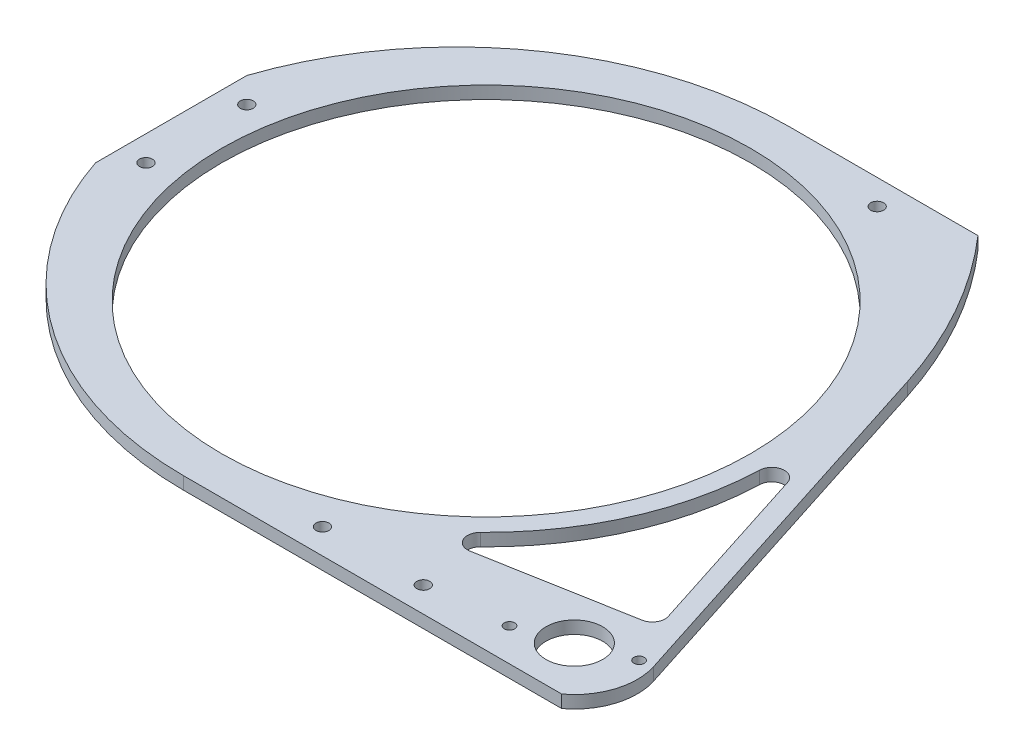
SolidWorks part; units mm, degrees
material "3003 Alloy"
ref_plane "Front Plane" through (0, 0, 0) normal (0, 0, 1) x (1, 0, 0)
ref_plane "Top Plane" through (0, 0, 0) normal (0, 1, 0) x (1, 0, 0)
ref_plane "Right Plane" through (0, 0, 0) normal (1, 0, 0) x (0, 0, -1)
sketch "Sketch1" plane through (0, 0, 0) normal (0, 1, 0) x (1, 0, 0)
  line L0 (-145.923, 0) -> (69.977, 0) construction
  line L1 (0, 152.4) -> (95.377, 152.4)
  line L2 (-158.623, 38.1) -> (-158.623, -38.1)
  line L3 (0, -152.4) -> (95.377, -152.4)
  line L4 (152.4, 152.4) -> (152.4, -86.7552) construction
  line L5 (-133.223, -12.7) -> (-158.623, -12.7) construction
  line L6 (-133.223, -12.7) -> (-133.223, 12.7) construction
  line L7 (-133.223, 12.7) -> (-158.623, 12.7) construction
  line L8 (-158.623, -12.7) -> (-158.623, 12.7)
  line L9 (-133.223, -12.7) -> (-158.623, 12.7) construction
  line L10 (-133.223, 12.7) -> (-158.623, -12.7) construction
  line L11 (69.977, 0) -> (69.977, -127) construction
  line L12 (69.977, 0) -> (69.977, 127) construction
  line L13 (69.977, -127) -> (95.377, -127) construction
  line L14 (69.977, -127) -> (69.977, -152.4) construction
  line L15 (69.977, -152.4) -> (95.377, -152.4) construction
  line L16 (95.377, -127) -> (95.377, -152.4) construction
  line L17 (0, -1000) -> (0, 49000) construction
  line L18 (69.977, 127) -> (95.377, 127) construction
  line L19 (69.977, 127) -> (69.977, 152.4) construction
  line L20 (69.977, 152.4) -> (95.377, 152.4) construction
  line L21 (95.377, 127) -> (95.377, 152.4) construction
  line L22 (-145.923, 0) -> (-145.923, 25.4) construction
  line L23 (-145.923, 0) -> (-145.923, -25.4) construction
  line L24 (69.977, -152.4) -> (95.377, -127) construction
  line L25 (95.377, -152.4) -> (69.977, -127) construction
  line L26 (69.977, 127) -> (95.377, 152.4) construction
  line L27 (95.377, 127) -> (69.977, 152.4) construction
  line L28 (0, 0) -> (171.4453, -127) construction
  line L29 (119.2718, -146.2694) -> (106.8922, -150.8416) construction
  line L30 (-904.623, -152.4) -> (49095.377, -152.4) construction
  line L31 (131.1096, -97.1209) -> (21047.5393, 45317.6671) construction
  line L32 (171.4453, -127) -> (162.6452, -103.1731) construction
  line L33 (147.6184, -135.8001) -> (162.6452, -103.1731) construction
  line L34 (171.4453, -152.4) -> (95.377, -152.4)
  line L35 (171.4453, -152.4) -> (190.4953, -152.4)
  line L36 (150.2632, 42.9852) -> (-15121.6052, 47653.5936) construction
  line L37 (201.678, -117.3024) -> (141.3054, 70.9116)
  line L38 (82.677, -139.7) -> (108.077, -139.7) construction
  circle A0 centre (0, 0) radius 127 construction
  circle A1 centre (0, 0) radius 133.223
  arc A2 (-158.623, 38.1) -> (0, 152.4) centre (0, -14.8167) cw
  arc A3 (-158.623, -38.1) -> (0, -152.4) centre (0, 14.8167) ccw
  circle A4 centre (-145.923, 25.4) radius 3.2639
  circle A5 centre (-145.923, -25.4) radius 3.2639
  circle A6 centre (57.277, 139.7) radius 3.2639
  circle A7 centre (57.277, -139.7) radius 3.2639
  arc A8 (95.377, 152.4) -> (95.377, -152.4) centre (-79.7641, 0) cw construction
  circle A9 centre (171.4453, -127) radius 25.4 construction
  circle A10 centre (147.6184, -135.8001) radius 2.6289
  circle A11 centre (195.2721, -118.1999) radius 2.6289
  circle A12 centre (171.4453, -127) radius 14.2875
  arc A13 (190.4953, -152.4) -> (201.2289, -115.9999) centre (171.4453, -127) ccw
  arc A14 (95.377, 152.4) -> (141.3054, 70.9116) centre (-79.7641, 0) cw
  circle A15 centre (108.077, -139.7) radius 3.2639
  point P4 (-145.923, 0)
  point P24 (-158.623, 38.1)
  point P31 (-158.623, -38.1)
  point P38 (82.677, 139.7)
  point P41 (82.677, -139.7)
  point P55 (131.1096, -97.1209)
  point P58 (171.4453, -152.4)
  point P64 (201.678, -117.3024)
  dimension "D1" = 254
  dimension "D12" = 152.4
  dimension "D15" = 25.4
  dimension "D16" = 6.5278
  dimension "D18" = 6.5278
  dimension "D21" = 6.5278
  dimension "D24" = 6.5278
  dimension "D26" = 50.8
  dimension "D27" = 5.2578
  dimension "D28" = 5.2578
  dimension "D29" = 28.575
  dimension "D30" = 63.5
  dimension "D32" = 6.5278
  dimension "D3" = 25.4
  dimension "D4" = 25.4
  dimension "D5" = 25.4
  dimension "D6" = 215.9
  dimension "D7" = 127
  dimension "D8" = 25.4
  dimension "D9" = 25.4
  dimension "D10" = 127
  dimension "D11" = 25.4
  dimension "D13" = 25.4
  dimension "D14" = 25.4
  dimension "D17" = 25.4
  dimension "D19" = 12.7
  dimension "D20" = 25.4
  dimension "D22" = 12.7
  dimension "D23" = 25.4
  dimension "D25" = 213.36
  dimension "D31" = 25.4
  dimension "D2" = 6.223
extrude "Boss-Extrude1" add sketch "Sketch1" along normal blind 6.35 contours A8 L1 A2 L2 A3 L3 A7 A6 A5 A4 A1 region at (47.6885, 0, -147.6691)
sketch "Sketch2" plane through (0, 6.35, 0) normal (0, 1, 0) x (1, 0, 0)
  line L0 (0, -152.4) -> (190.4953, -152.4) construction
  line L1 (69.977, -152.4) -> (95.377, -152.4) construction
  line L2 (69.977, -152.4) -> (69.977, -127) construction
  line L3 (69.977, -127) -> (95.377, -127) construction
  line L4 (95.377, -152.4) -> (95.377, -127) construction
  line L11 (81.0963, -117.475) -> (185.6838, -98.6244)
  line L13 (142.748, 0) -> (142.748, 35.2294)
  line L14 (201.678, -117.3024) -> (141.3054, 70.9116) construction
  line L15 (142.748, 35.2294) -> (185.6838, -98.6244)
  line L16 (142.748, 0) -> (0, 0) construction
  circle A0 centre (57.277, -139.7) radius 3.2639 construction
  circle A1 centre (57.277, -139.7) radius 3.2639 construction
  arc A2 (81.0963, -117.475) -> (142.748, 0) centre (0, 0) ccw
  circle A3 centre (0, 0) radius 133.223 construction
  circle A5 centre (171.4453, -127) radius 14.2875 construction
  dimension "D4" = 9.525
  dimension "D6" = 9.525
  dimension "D1" = 25.4
  dimension "D2" = 25.4
  dimension "D3" = 12.7
  dimension "D5" = 25.4
  dimension "D7" = 9.525
extrude "Cut-Extrude1" cut sketch "Sketch2" against normal blind 6.35
fillet "Fillet1" radius 6.35 3 edges at (81.0963, 3.175, 117.475) (142.748, 3.175, -35.2294) (185.6838, 3.175, 98.6244)
